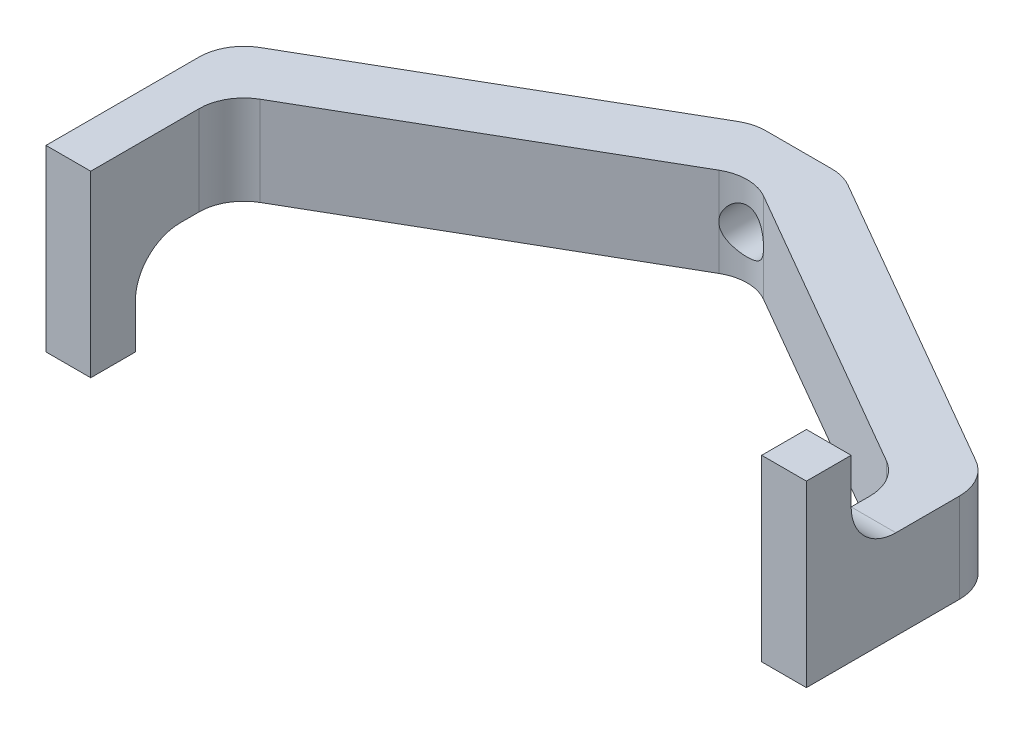
SolidWorks part; units mm, degrees
ref_plane "Front Plane" through (0, 0, 0) normal (0, 0, 1) x (1, 0, 0)
ref_plane "Top Plane" through (0, 0, 0) normal (0, 1, 0) x (1, 0, 0)
ref_plane "Right Plane" through (0, 0, 0) normal (1, 0, 0) x (0, 0, -1)
sketch "Sketch1" plane through (0, 0, 0) normal (0, 0, 1) x (1, 0, 0)
  line L0 (-42.5, 0) -> (42.5, 0) construction
  line L1 (-37.5, 5) -> (-42.5, 5)
  line L2 (-37.5, 5) -> (-37.5, -5)
  line L3 (-37.5, -5) -> (-42.5, -5)
  line L4 (-42.5, 5) -> (-42.5, -5)
  line L5 (42.5, 5) -> (37.5, 5)
  line L6 (42.5, 5) -> (42.5, -5)
  line L7 (42.5, -5) -> (37.5, -5)
  line L8 (37.5, 5) -> (37.5, -5)
  point P10 (30.1064, -8.0319)
  point P11 (-33.1915, 8.1383)
  dimension "D1" = 5
  dimension "D2" = 10
  dimension "D3" = 75
extrude "Boss-Extrude1" add sketch "Sketch1" along normal mid plane 10
sketch "Sketch2" plane through (0, 0, 5) normal (0, 0, 1) x (1, 0, 0)
  line L1 (-42.5, 5) -> (-37.5, 5)
  line L2 (-42.5, 5) -> (-42.5, -15)
  line L3 (-42.5, -15) -> (-37.5, -15)
  line L4 (-37.5, 5) -> (-37.5, -15)
  line L5 (42.5, -5) -> (37.5, -5)
  line L6 (42.5, -5) -> (42.5, 15)
  line L7 (42.5, 15) -> (37.5, 15)
  line L8 (37.5, -5) -> (37.5, 15)
  dimension "D1" = 20
extrude "Boss-Extrude2" add sketch "Sketch2" along normal blind 5
sketch "Sketch3" plane through (0, 5, 0) normal (0, 1, 0) x (1, 0, 0)
  line L0 (-37.5, 5) -> (0, 26.6506)
  line L1 (0, 26.6506) -> (37.5, 5)
  line L2 (37.5, 5) -> (42.5, 5)
  line L5 (-42.5, 10) -> (-42.5, 5)
  line L6 (-42.5, 5) -> (-37.5, 5)
  line L8 (42.5, 10) -> (42.5, 5)
  line L9 (-42.5, -10) -> (-42.5, 5) construction
  line L10 (-42.5, 10) -> (-5, 31.6506)
  line L11 (-5, 31.6506) -> (5, 31.6506)
  line L12 (5, 31.6506) -> (42.5, 10)
  point P3 (0, 31.6506)
  point P13 (-5, 31.2125)
  dimension "D1" = 30
  dimension "D2" = 10
  dimension "D3" = 5
extrude "Boss-Extrude3" add sketch "Sketch3" against normal up to surface (10 mm away) up to face at (40, -5, 2.5)
sketch "Sketch4" plane through (0, 0, -31.6506) normal (0, 0, -1) x (-1, 0, 0)
  circle A0 centre (0, 0) radius 2.5
  dimension "D1" = 5
extrude "Cut-Extrude1" cut sketch "Sketch4" against normal through all
fillet "Fillet1" radius 5 10 edges at (-40, -5, 5) (40, 5, 5) (0, 3.75, -26.6506) (0, -3.75, -26.6506) (-5, 0, -31.6506) (5, 0, -31.6506) (42.5, 0, -10) (-42.5, 0, -10) (37.5, 0, -5) (-37.5, 0, -5)
sketch "Sketch5" plane through (0, 5, 0) normal (0, 1, 0) x (1, 0, 0)
  line L0 (0, 25.8771) -> (0, 31.6506) construction
  line L1 (3.6603, 31.6506) -> (-3.6603, 31.6506) construction
  circle A0 centre (0, 28.7639) radius 1.5
  arc A1 (2.5, 25.2073) -> (-2.5, 25.2073) centre (0, 20.8771) ccw construction
  dimension "D1" = 3
extrude "Cut-Extrude2" [suppressed] cut sketch "Sketch5" against normal through all
